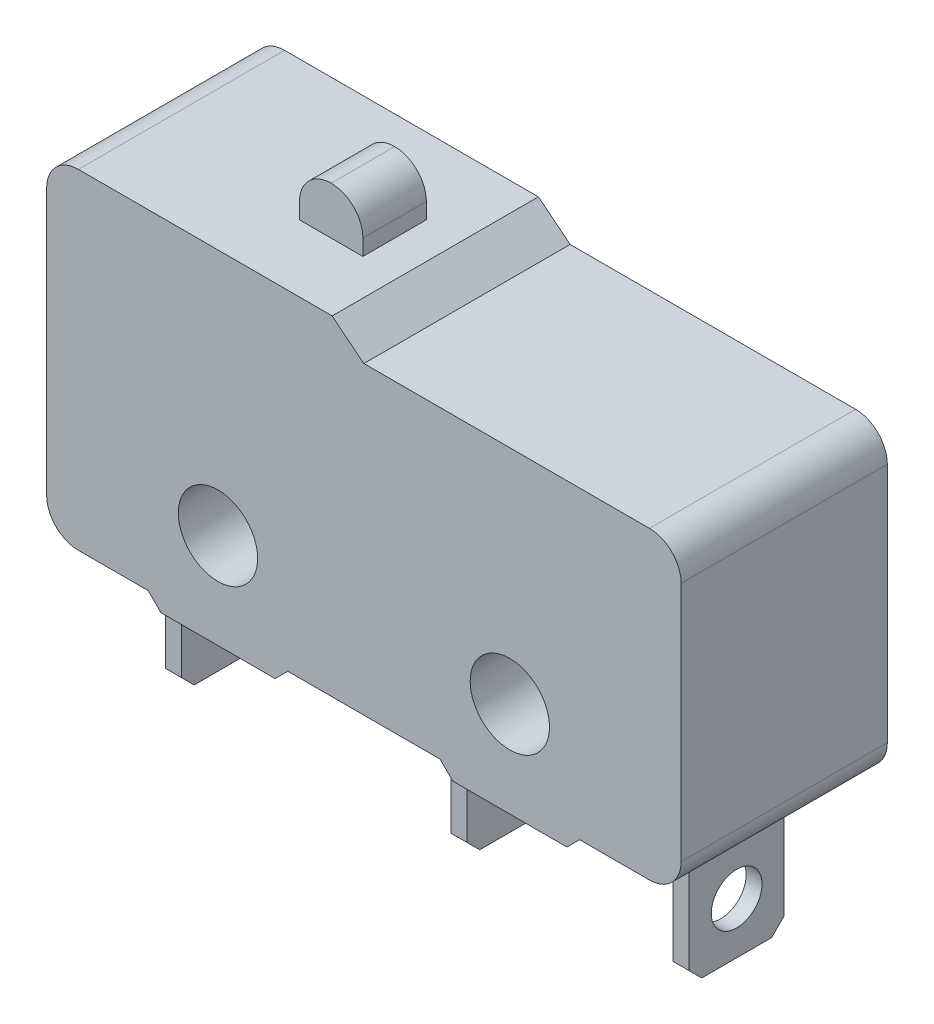
SolidWorks part; units mm, degrees
ref_plane "Front Plane" through (0, 0, 0) normal (0, 0, 1) x (1, 0, 0)
ref_plane "Top Plane" through (0, 0, 0) normal (0, 1, 0) x (1, 0, 0)
ref_plane "Right Plane" through (0, 0, 0) normal (1, 0, 0) x (0, 0, -1)
sketch "Sketch2" plane through (0, 0, 0) normal (0, 0, 1) x (1, 0, 0)
  line L0 (0, 9.8) -> (0, 1.4)
  line L1 (0, -55) -> (0, 55) construction
  line L2 (1, 10.8) -> (9, 10.8)
  line L3 (3.6, 0) -> (7.2, 0)
  line L5 (20, 1.4) -> (20, 9)
  line L6 (19, 10) -> (10, 10)
  line L7 (10, 10) -> (9, 10.8)
  line L8 (12.8, 0) -> (16.4, 0)
  line L9 (19, 0.4) -> (16.4, 0.4)
  line L10 (16.4, 0.4) -> (16.4, 0)
  line L11 (16.4, 0) -> (12.8, 0)
  line L12 (12.8, 0) -> (12.8, 0.4)
  line L13 (12.8, 0.4) -> (7.2, 0.4)
  line L14 (3.6, 0.4) -> (1, 0.4)
  line L15 (7.2, 0) -> (7.2, 0.4)
  line L16 (3.6, 0) -> (7.2, 0)
  line L17 (3.6, 0.4) -> (3.6, 0)
  arc A0 (1, 0.4) -> (0, 1.4) centre (1, 1.4) cw
  arc A1 (20, 1.4) -> (19, 0.4) centre (19, 1.4) cw
  arc A2 (20, 9) -> (19, 10) centre (19, 9) ccw
  arc A3 (0, 9.8) -> (1, 10.8) centre (1, 9.8) cw
  circle A4 centre (5.4, 3) radius 1.25
  circle A5 centre (14.6, 3) radius 1.25
  point P25 (0, 10.8)
  dimension "D2" = 1
  dimension "D1" = 3.6
extrude "Boss-Extrude1" add sketch "Sketch2" along normal blind 6.5 contours A3 L0 A0 L14 L17 L3 L15 L13 L12 L8 L10 L9 A1 L5 A2 L6 L7 L2 A5 A4 region at (9.7921, 5.4424, 0)
chamfer "Chamfer1" distance 0.4 angle 45 4 edges at (3.6, 0.4, 3.25) (7.2, 0.4, 3.25) (12.8, 0.4, 3.25) (16.4, 0.4, 3.25)
sketch "Sketch3" plane through (0, 10.8, 0) normal (0, 1, 0) x (1, 0, 0)
  line L3 (5.8616, -4.3931) -> (7.8616, -4.3931)
  line L4 (5.8616, -4.3931) -> (5.8616, -2.3931)
  line L5 (5.8616, -2.3931) -> (7.8616, -2.3931)
  line L6 (7.8616, -4.3931) -> (7.8616, -2.3931)
  line L7 (5.8616, -4.3931) -> (7.8616, -2.3931) construction
  line L8 (5.8616, -2.3931) -> (7.8616, -4.3931) construction
  dimension "D1" = 2
  dimension "D2" = 2
extrude "Boss-Extrude2" add sketch "Sketch3" along normal blind 1.5
fillet "Fillet1" radius 1 2 edges at (5.8616, 12.3, 3.3931) (7.8616, 12.3, 3.3931)
sketch "Sketch4" plane through (0, 0.4, 0) normal (0, -1, 0) x (1, 0, 0)
  line L2 (2, 3.25) -> (2, 4.75)
  line L3 (2, 4.75) -> (2.5, 4.75)
  line L4 (2.5, 4.75) -> (2.5, 1.75)
  line L5 (2.5, 1.75) -> (2.0379, 1.75)
  line L6 (2.0379, 1.75) -> (2, 3.25)
  line L7 (11, 3.25) -> (11, 4.75)
  line L8 (11, 4.75) -> (11.5, 4.75)
  line L9 (11.5, 4.75) -> (11.5, 1.75)
  line L10 (11.5, 1.75) -> (11, 1.75)
  line L11 (11, 1.75) -> (11, 3.25)
  line L12 (18, 3.25) -> (18, 4.75)
  line L13 (18, 4.75) -> (18.5, 4.75)
  line L14 (18.5, 4.75) -> (18.5, 1.75)
  line L15 (18.5, 1.75) -> (18, 1.75)
  line L16 (18, 1.75) -> (18, 3.25)
extrude "Boss-Extrude3" add sketch "Sketch4" along normal blind 4
chamfer "Chamfer2" distance 0.4 angle 45 6 edges at (2.25, -3.6, 4.75) (18.25, -3.6, 4.75) (11.25, -3.6, 4.75) (2.2689, -3.6, 1.75) (18.25, -3.6, 1.75) (11.25, -3.6, 1.75)
sketch "Sketch5" plane through (18.5, 0, 0) normal (1, 0, 0) x (0, 0, -1)
  circle A0 centre (-3.25, -1.9831) radius 0.8
extrude "Cut-Extrude2" cut sketch "Sketch5" against normal blind 18
sketch "Sketch6" plane through (0, 0, 0) normal (0, 0, -1) x (-1, 0, 0)
  text T0 "5A250VAC" font "Century Gothic" height in points 8
extrude "Boss-Extrude4" add sketch "Sketch6" along normal blind 0.1
sketch "Esboço1" plane through (0, 0, 6.5) normal (0, 0, 1) x (1, 0, 0)
  line L0 (1, 10.8) -> (15.1892, 14.5125)
  line L1 (15.1892, 14.5125) -> (22.9287, 16.5375) construction
  line L2 (19.5525, 13.6385) -> (18.4261, 17.9436) construction
  line L3 (1.0253, 10.7033) -> (15.2755, 14.4317)
  line L4 (0.9747, 10.8967) -> (15.1039, 14.5936)
  arc A0 (22.9287, 16.5375) -> (15.1892, 14.5125) centre (19.5525, 13.6385) ccw
  arc A1 (6.8616, 12.3) -> (5.8616, 11.3) centre (6.8616, 11.3) ccw construction
  arc A2 (22.8528, 16.4724) -> (15.2755, 14.4317) centre (19.5525, 13.6385) ccw
  arc A3 (23.0045, 16.6027) -> (15.1039, 14.5936) centre (19.5525, 13.6385) ccw
  arc A4 (1.0253, 10.7033) -> (0.9747, 10.8967) centre (1, 10.8) cw
  arc A5 (22.8528, 16.4724) -> (23.0045, 16.6027) centre (22.9287, 16.5375) ccw
  dimension "D2" = 8
  dimension "D1" = 2.5
  dimension "D3" = 0.1
  dimension "D4" = 0.1
